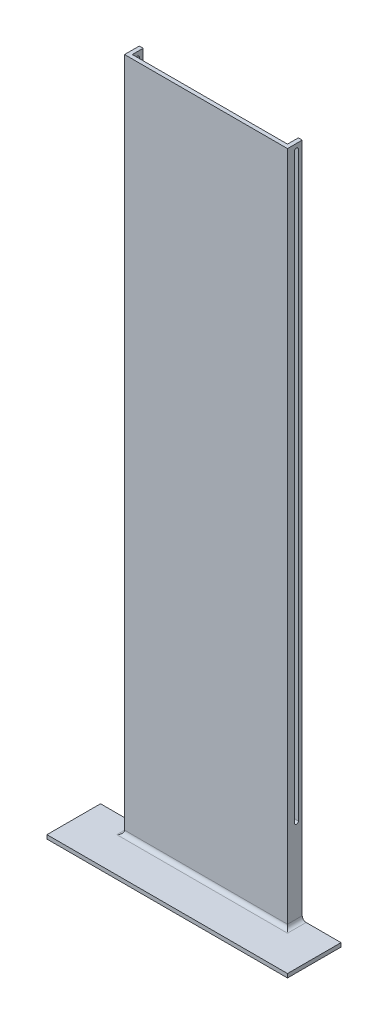
SolidWorks part; units mm, degrees
material "AISI 4340 Steel, annealed"
ref_plane "Front Plane" through (0, 0, 0) normal (0, 0, 1) x (1, 0, 0)
ref_plane "Top Plane" through (0, 0, 0) normal (0, 1, 0) x (1, 0, 0)
ref_plane "Right Plane" through (0, 0, 0) normal (1, 0, 0) x (0, 0, -1)
sketch "Sketch1" plane through (0, 0, 0) normal (1, 0, 0) x (0, 0, -1)
  line L0 (0, 0) -> (-100, 0)
  line L1 (-100, 0) -> (-100, -10)
  line L2 (-100, -10) -> (10, -10)
  line L3 (10, -10) -> (10, 1741.5)
  line L4 (10, 1741.5) -> (0, 1741.5)
  line L5 (0, 1741.5) -> (0, 0)
  dimension "D1" = 1751.5
  dimension "D2" = 10
  dimension "D3" = 10
  dimension "D4" = 100
extrude "Wall extrude" add sketch "Sketch1" along normal mid plane 400
sketch "Sketch2" plane through (200, 0, 0) normal (1, 0, 0) x (0, 0, -1)
  line L1 (10, 1741.5) -> (0, 1741.5) construction
  line L2 (10, -10) -> (10, 1741.5) construction
  line L3 (-100, -10) -> (10, -10) construction
  line L4 (0, 1741.5) -> (38, 1741.5)
  line L5 (0, 1741.5) -> (0, -10)
  line L6 (0, -10) -> (38, -10)
  line L7 (38, 1741.5) -> (38, -10)
  line L8 (18, 226.5) -> (18, 1726.5)
  line L9 (28, 1726.5) -> (28, 226.5)
  arc A0 (28, 1726.5) -> (18, 1726.5) centre (23, 1726.5) ccw
  arc A1 (18, 226.5) -> (28, 226.5) centre (23, 226.5) ccw
  dimension "D1" = 10
  dimension "D5" = 10
  dimension "D2" = 13
  dimension "D3" = 15
  dimension "D4" = 15
  dimension "D6" = 13
  dimension "D7" = 236.5
extrude "Right guide extrude" add sketch "Sketch2" along normal blind 10
mirror "Left guide extrude" about plane through (0, 0, 0) normal (1, 0, 0) of "Right guide extrude"
sketch "Sketch3" plane through (0, -10, 0) normal (0, -1, 0) x (1, 0, 0)
  line L0 (-210, -38) -> (-310, -38)
  line L1 (-310, -38) -> (-310, 100)
  line L2 (-310, 100) -> (-200, 100)
  line L3 (200, 100) -> (310, 100)
  line L4 (310, 100) -> (310, -38)
  line L5 (310, -38) -> (210, -38)
  line L12 (-200, 100) -> (-200, 0)
  line L13 (-200, 0) -> (-210, 0)
  line L14 (-210, 0) -> (-210, -38)
  line L15 (-210, -38) -> (-200, -38)
  line L16 (-200, -38) -> (-200, -10)
  line L17 (-200, -10) -> (200, -10)
  line L18 (200, -10) -> (200, -38)
  line L19 (200, -38) -> (210, -38)
  line L20 (210, -38) -> (210, 0)
  line L21 (210, 0) -> (200, 0)
  line L22 (200, 0) -> (200, 100)
  line L23 (200, 100) -> (-200, 100)
  line L24 (-200, 100) -> (-200, 0)
  line L25 (-200, 0) -> (-210, 0)
  line L26 (-210, 0) -> (-210, -38)
  line L32 (210, -38) -> (210, 0)
  line L33 (210, 0) -> (200, 0)
  line L34 (200, 0) -> (200, 100)
  dimension "D2" = 100
  dimension "D3" = 100
  dimension "D1" = 0
extrude "Bottom foot completion" add sketch "Sketch3" against normal blind 10
sketch "Sketch4" plane through (0, 0, -10) normal (0, 0, -1) x (-1, 0, 0)
  line L0 (-200, -10) -> (-200, 1741.5) construction
  line L1 (-200, 136.5) -> (200, 136.5)
  line L2 (-200, 136.5) -> (-200, 126.5)
  line L3 (-200, 126.5) -> (200, 126.5)
  line L4 (200, 136.5) -> (200, 126.5)
  line L5 (200, -10) -> (200, 1741.5) construction
  line L6 (-200, -10) -> (200, -10) construction
  dimension "D1" = 146.5
  dimension "D2" = 10
extrude "Platform stopper" add sketch "Sketch4" along normal up to surface (28 mm away) up to face at (240, 577.1667, -38)
fillet "Structural fillets" radius 10 6 edges at (-210, 0, -19) (210, 0, -19) (0, 0, 0) (-200, 126.5, -24) (200, 126.5, -24) (0, 126.5, -10)
